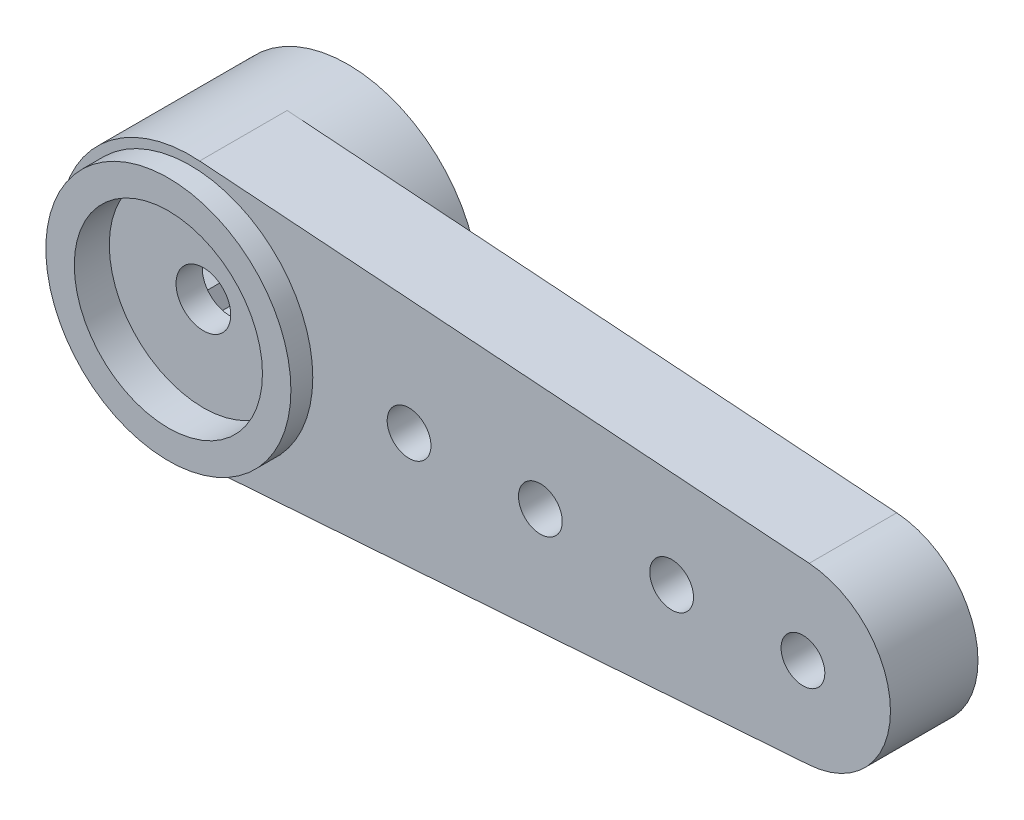
SolidWorks part; units mm, degrees
ref_plane "Front Plane" through (0, 0, 0) normal (0, 0, 1) x (1, 0, 0)
ref_plane "Top Plane" through (0, 0, 0) normal (0, 1, 0) x (1, 0, 0)
ref_plane "Right Plane" through (0, 0, 0) normal (1, 0, 0) x (0, 0, -1)
sketch "Sketch2" plane through (0, 0, 0) normal (0, 0, 1) x (1, 0, 0)
  line L0 (0, 0) -> (0, 4.5292) construction
  line L1 (0, 2) -> (0.3742, 1.7607)
  line L2 (2.6643, 5.984) -> (0, 0) construction
  line L3 (0.3742, 1.7607) -> (0.8135, 1.8271)
  line L4 (0.3742, 1.7607) -> (0.4158, 1.9563)
  line L33 (0.8135, 1.8271) -> (1.058, 1.4562)
  line L34 (1.058, 1.4562) -> (1.4863, 1.3383)
  line L35 (1.4863, 1.3383) -> (1.5588, 0.9)
  line L36 (1.5588, 0.9) -> (1.9021, 0.618)
  line L37 (1.9021, 0.618) -> (1.7901, 0.1882)
  line L38 (1.7901, 0.1882) -> (1.989, -0.2091)
  line L39 (1.989, -0.2091) -> (1.7119, -0.5562)
  line L40 (1.7119, -0.5562) -> (1.7321, -1)
  line L41 (1.7321, -1) -> (1.3377, -1.2044)
  line L42 (1.3377, -1.2044) -> (1.1756, -1.618)
  line L43 (1.1756, -1.618) -> (0.7321, -1.6444)
  line L44 (0.7321, -1.6444) -> (0.4158, -1.9563)
  line L45 (0.4158, -1.9563) -> (0, -1.8)
  line L46 (0, -1.8) -> (-0.4158, -1.9563)
  line L47 (-0.4158, -1.9563) -> (-0.7321, -1.6444)
  line L48 (-0.7321, -1.6444) -> (-1.1756, -1.618)
  line L49 (-1.1756, -1.618) -> (-1.3377, -1.2044)
  line L50 (-1.3377, -1.2044) -> (-1.7321, -1)
  line L51 (-1.7321, -1) -> (-1.7119, -0.5562)
  line L52 (-1.7119, -0.5562) -> (-1.989, -0.2091)
  line L53 (-1.989, -0.2091) -> (-1.7901, 0.1882)
  line L54 (-1.7901, 0.1882) -> (-1.9021, 0.618)
  line L55 (-1.9021, 0.618) -> (-1.5588, 0.9)
  line L56 (-1.5588, 0.9) -> (-1.4863, 1.3383)
  line L57 (-1.4863, 1.3383) -> (-1.058, 1.4562)
  line L58 (-1.058, 1.4562) -> (-0.8135, 1.8271)
  line L59 (-0.8135, 1.8271) -> (-0.3742, 1.7607)
  line L60 (-0.3742, 1.7607) -> (0, 2)
  line L61 (0.2143, 2.9923) -> (14.1429, 1.9949)
  line L62 (0.2143, -2.9923) -> (14.1429, -1.9949)
  circle A0 centre (0, 0) radius 2.8
  circle A1 centre (0, 0) radius 3
  circle A2 centre (0, 0) radius 2 construction
  circle A3 centre (0, 0) radius 0.625
  circle A4 centre (0, 0) radius 2.15
  circle A5 centre (14, 0) radius 2
  circle A6 centre (14, 0) radius 0.5
  circle A7 centre (11, 0) radius 0.5
  circle A8 centre (8, 0) radius 0.5
  circle A9 centre (5, 0) radius 0.5
  point P11 (0.8135, 1.8271)
  point P51 (0, 0)
  point P57 (0, 0)
  dimension "D1" = 6
  dimension "D2" = 5.6
  dimension "D3" = 4
  dimension "D7" = 1.25
  dimension "D9" = 4.3
  dimension "D10" = 4
  dimension "D12" = 1
  dimension "D4" = 24
  dimension "D5" = 12
  dimension "D6" = 0.2
  dimension "D11" = 14
  dimension "D13" = 3
  dimension "D14" = 3
  dimension "D15" = 3
  dimension "D8" = 15
extrude "Boss-Extrude1" add sketch "Sketch2" along normal blind 3.6 contours A1 A0 region at (2.1337, 1.9863, 0)
extrude "Boss-Extrude2" add sketch "Sketch2<3>" along normal blind 4.1 contours A4 | A0
sketch "Sketch2<3>" plane through (0, 0, 0) normal (0, 0, 1) x (1, 0, 0) same geometry as "Sketch2"
extrude "Boss-Extrude3" add sketch "Sketch2<4>" along normal blind 0.6 from offset 2.7 contours A4 L59 L60 L1 L3 L33 L34 L35 L36 L37 L38 L39 L40 L41 L42 L43 L44 L45 L46 L47 L48 L49 L50 L51 L52 L53 L54 L55 L56 L57 L58 | L60 L59 L58 L57 L56 L55 L54 L53 L52 L51 L50 L49 L48 L47 L46 L45 L44 L43 L42 L41 L40 L39 L38 L37 L36 L35 L34 L33 L3 L1 A3 region at (0.1569, 1.8331, 0) region at (-2.0892, 0, 0)
sketch "Sketch2<4>" plane through (0, 0, 0) normal (0, 0, 1) x (1, 0, 0) same geometry as "Sketch2"
extrude "Boss-Extrude4" add sketch "Sketch2<5>" along normal up to surface (2.7 mm away) contours A4 L59 L60 L1 L3 L33 L34 L35 L36 L37 L38 L39 L40 L41 L42 L43 L44 L45 L46 L47 L48 L49 L50 L51 L52 L53 L54 L55 L56 L57 L58 region at (-2.0892, 0, 0) up to face at (2.15, 0, 2.7)
sketch "Sketch2<5>" plane through (0, 0, 0) normal (0, 0, 1) x (1, 0, 0) same geometry as "Sketch2"
extrude "Boss-Extrude5" add sketch "Sketch2<6>" against normal blind 2 from surface contours A5 L61 A1 L62 | A5 A6 region at (7.1522, 0, 0) region at (15.4224, 1.3242, 0) starting at face at (2.8, 0, 3.6)
sketch "Sketch2<6>" plane through (0, 0, 0) normal (0, 0, 1) x (1, 0, 0) same geometry as "Sketch2"
